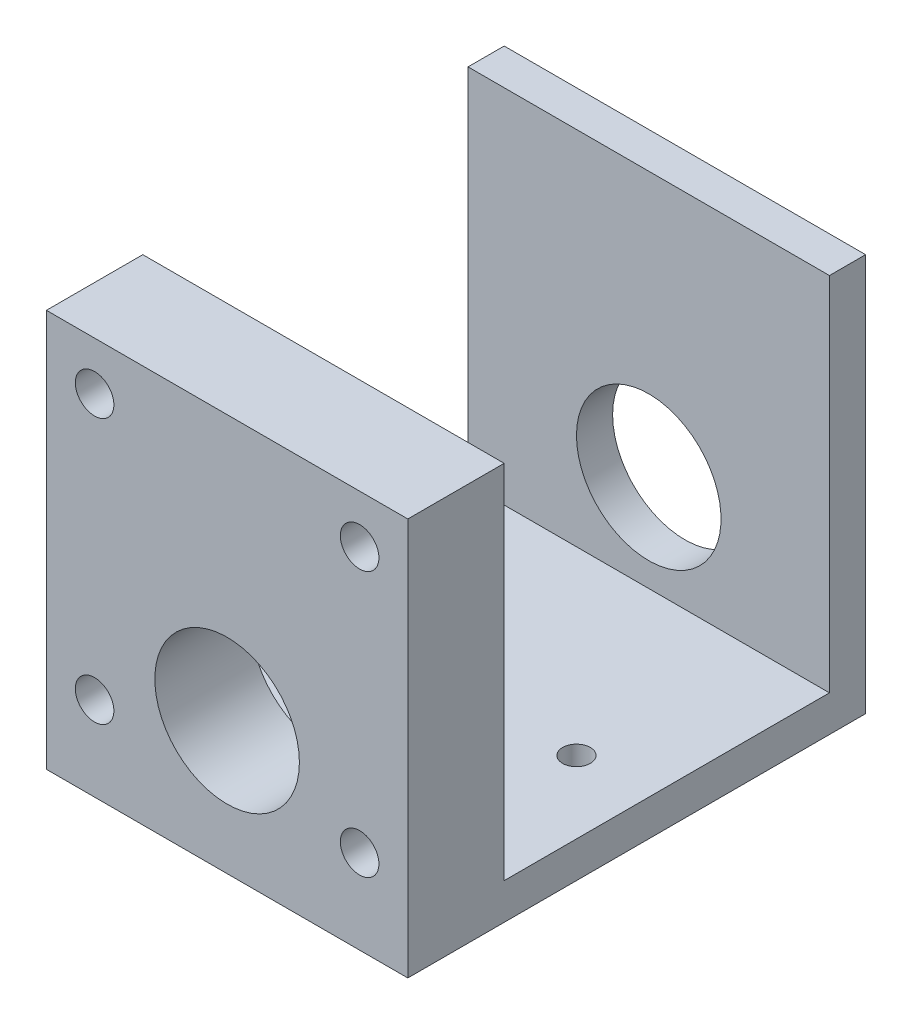
SolidWorks part; units mm, degrees
ref_plane "Front Plane" through (0, 0, 0) normal (0, 0, 1) x (1, 0, 0)
ref_plane "Top Plane" through (0, 0, 0) normal (0, 1, 0) x (1, 0, 0)
ref_plane "Right Plane" through (0, 0, 0) normal (1, 0, 0) x (0, 0, -1)
sketch "Sketch1" plane through (0, 0, 0) normal (0, 1, 0) x (1, 0, 0)
  line L1 (0, 0) -> (30, 0)
  line L2 (0, 0) -> (0, 30)
  line L3 (0, 30) -> (30, 30)
  line L4 (30, 0) -> (30, 30)
  circle A0 centre (6, 12) radius 1.15
  circle A1 centre (24, 12) radius 1.15
  dimension "D2" = 2.3
  dimension "D3" = 2.3
  dimension "D4" = 18
  dimension "D7" = 18
  dimension "D1" = 30
  dimension "D5" = 6
  dimension "D6" = 30
extrude "Boss-Extrude1" add sketch "Sketch1" along normal blind 3
sketch "Sketch2" plane through (0, 3, 0) normal (0, 1, 0) x (1, 0, 0)
  line L0 (0, 30) -> (0, 0) construction
  line L1 (30, 30) -> (0, 30)
  line L2 (30, 30) -> (30, 27)
  line L3 (30, 27) -> (0, 27)
  line L4 (0, 30) -> (0, 27)
  dimension "D1" = 3
extrude "Boss-Extrude2" add sketch "Sketch2" along normal blind 30
sketch "Sketch3" plane through (0, 0, -30) normal (0, 0, -1) x (-1, 0, 0)
  line L0 (-30, 0) -> (0, 0) construction
  line L1 (-30, 33) -> (-30, 0) construction
  circle A0 centre (-15, 11) radius 6
  dimension "D1" = 11
  dimension "D2" = 12
  dimension "D3" = 15
extrude "Cut-Extrude1" cut sketch "Sketch3" against normal up to next
sketch "Sketch4" plane through (0, 0, 0) normal (0, 0, 1) x (1, 0, 0)
  line L1 (30, 0) -> (0, 0)
  line L2 (30, 0) -> (30, 33)
  line L3 (30, 33) -> (0, 33)
  line L4 (0, 0) -> (0, 33)
  circle A0 centre (15, 11) radius 6
  dimension "D2" = 12
  dimension "D1" = 33
extrude "Boss-Extrude3" add sketch "Sketch4" along normal blind 3
sketch "Sketch5" plane through (0, 0, 3) normal (0, 0, 1) x (1, 0, 0)
  line L0 (30, 0) -> (30, 33) construction
  line L1 (26, 7) -> (4, 7) construction
  line L2 (26, 7) -> (26, 29) construction
  line L3 (26, 29) -> (4, 29) construction
  line L4 (4, 7) -> (4, 29) construction
  line L5 (0, 0) -> (30, 0) construction
  circle A0 centre (26, 7) radius 1.6
  circle A1 centre (4, 7) radius 1.6
  circle A2 centre (4, 29) radius 1.6
  circle A3 centre (26, 29) radius 1.6
  dimension "D5" = 3.2
  dimension "D6" = 3.2
  dimension "D7" = 3.2
  dimension "D8" = 3.2
  dimension "D1" = 22
  dimension "D2" = 4
  dimension "D3" = 22
  dimension "D4" = 7
extrude "Cut-Extrude3" cut sketch "Sketch5" against normal up to next
sketch "Sketch6" plane through (0, 0, 3) normal (0, 0, 1) x (1, 0, 0)
  line L1 (0, 0) -> (30, 0)
  line L2 (0, 0) -> (0, 33)
  line L3 (0, 33) -> (30, 33)
  line L4 (30, 0) -> (30, 33)
  circle A0 centre (15, 11) radius 6
  circle A1 centre (4, 7) radius 1.6
  circle A2 centre (4, 29) radius 1.6
  circle A3 centre (26, 29) radius 1.6
  circle A4 centre (26, 7) radius 1.6
extrude "Boss-Extrude4" add sketch "Sketch6" along normal blind 5
